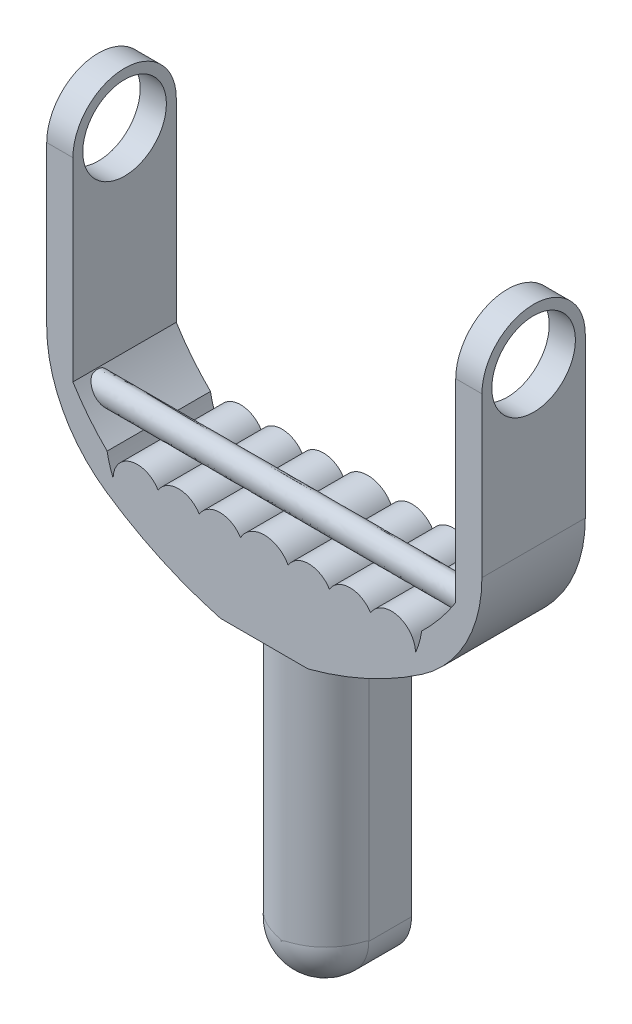
SolidWorks part; units mm, degrees
note: '?' marks a value the reader was unsure of.
ref_plane "Front Plane" through (0, 0, 0) normal (0, 0, 1) x (1, 0, 0)
ref_plane "Top Plane" through (0, 0, 0) normal (0, 1, 0) x (1, 0, 0)
ref_plane "Right Plane" through (0, 0, 0) normal (1, 0, 0) x (0, 0, -1)
ref_axis "X-Axis" through (-88.99, 0, 0) along (1, 0, 0)?
ref_axis "Y-Axis" through (0, 55, 0) along (0, -1, 0)?
ref_axis "Z-Axis" through (0, 0, 55) along (0, 0, -1)?
sketch "Sketch1" plane through (0, 0, 0) normal (0, 0, 1) x (1, 0, 0)
  line L0 (-8.0751, 8.0441) -> (-8.0751, 57.119)
  line L1 (-40.1043, 76.169) -> (-40.1043, 126.969)
  line L2 (-40.1043, 126.969) -> (-35.2783, 126.969)
  line L3 (-35.2783, 126.969) -> (-35.2783, 81.249)
  line L5 (-35.2783, 81.249) -> (35.2783, 81.249)
  line L7 (29.2433, 76.4865) -> (-29.2433, 76.4865)
  line L10 (8.0751, 8.0441) -> (8.0751, 57.119)
  line L11 (40.1043, 76.169) -> (40.1043, 126.969)
  line L12 (40.1043, 126.969) -> (35.2783, 126.969)
  line L13 (35.2783, 126.969) -> (35.2783, 81.249)
  line L14 (0, 81.249) -> (0, 106.6366) construction
  arc A0 (8.0751, 57.119) -> (40.1043, 76.169) centre (-9.5537, 123.2094) ccw
  arc A1 (8.0751, 8.0441) -> (-8.0751, 8.0441) centre (0, 8.0441) cw
  arc A2 (-29.2433, 76.4865) -> (-27.8621, 69.585) centre (-11.3104, 76.4865) ccw
  arc A3 (-19.5829, 71.8338) -> (-27.8621, 69.585) centre (-23.4171, 69.585) ccw
  arc A4 (-8.0751, 57.119) -> (-40.1043, 76.169) centre (9.5537, 123.2094) cw
  arc A5 (-11.9933, 71.8028) -> (-19.5829, 71.8338) centre (-15.7975, 69.5037) ccw
  arc A6 (-4.3802, 71.8333) -> (-11.9933, 71.8028) centre (-8.1775, 69.5229) ccw
  arc A8 (29.2433, 76.4865) -> (27.8621, 69.585) centre (11.3104, 76.4865) cw
  arc A9 (19.5829, 71.8338) -> (27.8621, 69.585) centre (23.4171, 69.585) cw
  arc A10 (11.9933, 71.8028) -> (19.5829, 71.8338) centre (15.7975, 69.5037) cw
  arc A11 (4.3802, 71.8333) -> (11.9933, 71.8028) centre (8.1775, 69.5229) cw
  arc A14 (-4.3802, 71.8333) -> (-4.3514, 71.887) centre (0, 69.5229) cw
  arc A15 (4.3802, 71.8333) -> (-4.3514, 71.887) centre (0, 69.5229) ccw
  dimension "D4" = 8.89
  dimension "D5" = 8.89
  dimension "D6" = 8.89
  dimension "D3" = 69.85
  dimension "D9" = 7.62
  dimension "D10" = 7.62
  dimension "D11" = 45.72
  dimension "D13" = 50.8
  dimension "D14" = 4.826
extrude "Boss-Extrude1" add sketch "Sketch1" along normal blind 19.05
fillet "Fillet1" radius 25.4 2 edges at (-40.1043, 76.169, 9.525) (40.1043, 76.169, 9.525)
sketch "Sketch2" plane through (40.1043, 0, 0) normal (1, 0, 0) x (0, 0, -1)
  line L0 (0, 87.7038) -> (0, 126.969) construction
  line L1 (-19.05, 87.7038) -> (-19.05, 126.969) construction
  line L2 (-19.05, 117.0506) -> (-19.05, 133.4837)
  line L3 (-19.05, 133.4837) -> (0, 133.4837)
  line L4 (0, 133.4837) -> (0, 117.0506)
  arc A0 (0, 117.0506) -> (-19.05, 117.0506) centre (-9.525, 117.0506) ccw
extrude "Cut-Extrude1" cut sketch "Sketch2" against normal through all
sketch "Sketch3" plane through (40.1043, 0, 0) normal (1, 0, 0) x (0, 0, -1)
  circle A0 centre (-9.525, 117.0506) radius 7.7064
extrude "Cut-Extrude2" cut sketch "Sketch3" against normal through all
sketch "Sketch4" plane through (0, 0, 0) normal (1, 0, 0) x (0, 0, -1)
  line L0 (-14.6826, 81.249) -> (0, 81.249)
  line L1 (0, 81.249) -> (0, 76.4865)
  line L3 (-19.05, 76.4865) -> (0, 76.4865) construction
  line L4 (0, 76.4865) -> (-14.6826, 76.4865)
  ellipse E0 centre (-14.6826, 78.8677) end of major axis (-14.6826, 81.249) minor radius 2.0419 (-14.6826, 76.4865) -> (-14.6826, 81.249) ccw
extrude "Cut-Extrude3" cut sketch "Sketch4" against normal mid plane 58.42
sketch "Sketch6" plane through (0, 0, 0) normal (1, 0, 0) x (0, 0, -1)
  line L0 (-14.6826, 76.4865) -> (-19.05, 76.4865)
  line L1 (-19.05, 87.7038) -> (-19.05, 66.7312) construction
  line L2 (-19.05, 76.4865) -> (0, 76.4865) construction
  line L3 (-19.05, 76.4865) -> (-19.05, 81.249)
  line L4 (-19.05, 81.249) -> (-14.6826, 81.249)
  ellipse E0 centre (-14.6826, 78.8677) end of major axis (-14.6826, 76.4865) minor radius 2.0419 (-14.6826, 81.249) -> (-14.6826, 76.4865) ccw
  ellipse E1 centre (-14.6826, 78.8677) end of major axis (-14.6826, 81.249) minor radius 2.0419 (-14.6826, 76.4865) -> (-14.6826, 81.249) ccw construction
extrude "Cut-Extrude9" cut sketch "Sketch6" against normal mid plane 58.42
sketch "Sketch7" plane through (0, 0, 0) normal (1, 0, 0) x (0, 0, -1)
  line L1 (-19.05, 57.119) -> (-15.8765, 57.119)
  line L2 (-19.05, 57.119) -> (-19.05, -2.4661)
  line L3 (-19.05, -2.4661) -> (-15.8765, -2.4661)
  line L4 (-15.8765, 57.119) -> (-15.8765, -2.4661)
extrude "Cut-Extrude10" cut sketch "Sketch7" against normal mid plane 58.42
sketch "Sketch8" plane through (0, 0, 19.05) normal (0, 0, 1) x (1, 0, 0)
  line L0 (29.21, 81.249) -> (35.2272, 81.249)
  line L1 (35.2783, 81.249) -> (29.21, 81.249) construction
  line L2 (29.21, 81.249) -> (29.0179, 73.6522)
  arc A0 (29.0179, 73.6522) -> (35.2272, 81.249) centre (0.411, 103.3705) ccw construction
  arc A1 (27.8621, 69.585) -> (29.2433, 76.4865) centre (11.3104, 76.4865) ccw construction
  arc A2 (29.0179, 73.6522) -> (35.2272, 81.249) centre (0.411, 103.3705) ccw
extrude "Cut-Extrude12" cut sketch "Sketch8" against normal up to body separate body
sketch "Sketch9" plane through (0, 0, 19.05) normal (0, 0, 1) x (1, 0, 0)
  line L0 (-29.21, 81.249) -> (-28.9711, 73.3741)
  line L1 (-29.21, 81.249) -> (-35.2783, 81.249)
  arc A0 (-35.2784, 81.249) -> (-28.9711, 73.3741) centre (0.411, 103.3705) ccw
  arc A1 (-29.2433, 76.4865) -> (-27.8621, 69.585) centre (-11.3104, 76.4865) ccw construction
sketch "Sketch10" plane through (0, 0, 0) normal (0, 0, -1) x (-1, 0, 0)
  line L0 (35.2784, 81.249) -> (29.21, 81.249)
  line L1 (29.21, 81.249) -> (28.9711, 73.3741)
  arc A0 (28.9711, 73.3741) -> (35.2784, 81.249) centre (-0.411, 103.3705) ccw
extrude "Cut-Extrude13" cut sketch "Sketch10" against normal blind 23.114
sketch "Sketch11" plane through (0, 0, 0) normal (1, 0, 0) x (0, 0, -1)
  ellipse E0 centre (-14.6826, 78.8677) end of major axis (-14.6826, 81.249) minor radius 2.0419
  ellipse E1 centre (-14.6826, 78.8677) end of major axis (-14.6826, 81.249) minor radius 2.0419 construction
extrude "Boss-Extrude4" add sketch "Sketch11" along normal up to body separate body
sketch "Sketch12" plane through (0, 0, 0) normal (1, 0, 0) x (0, 0, -1)
  ellipse E0 centre (-14.6826, 78.8677) end of major axis (-14.6826, 81.249) minor radius 2.0419
  ellipse E1 centre (-14.6826, 78.8677) end of major axis (-14.6826, 81.249) minor radius 2.0419 construction
extrude "Boss-Extrude8" add sketch "Sketch12" against normal blind 35.052 separate body
fillet "Fillet2" radius 8.0751 3 edges at (8.0751, 32.5815, 15.8765) (-8.0751, 32.5815, 15.8765) (0, 57.119, 15.8765)
fillet "Fillet3" radius 8.001 1 edges at (-8.0751, 8.0441, 15.8765)
